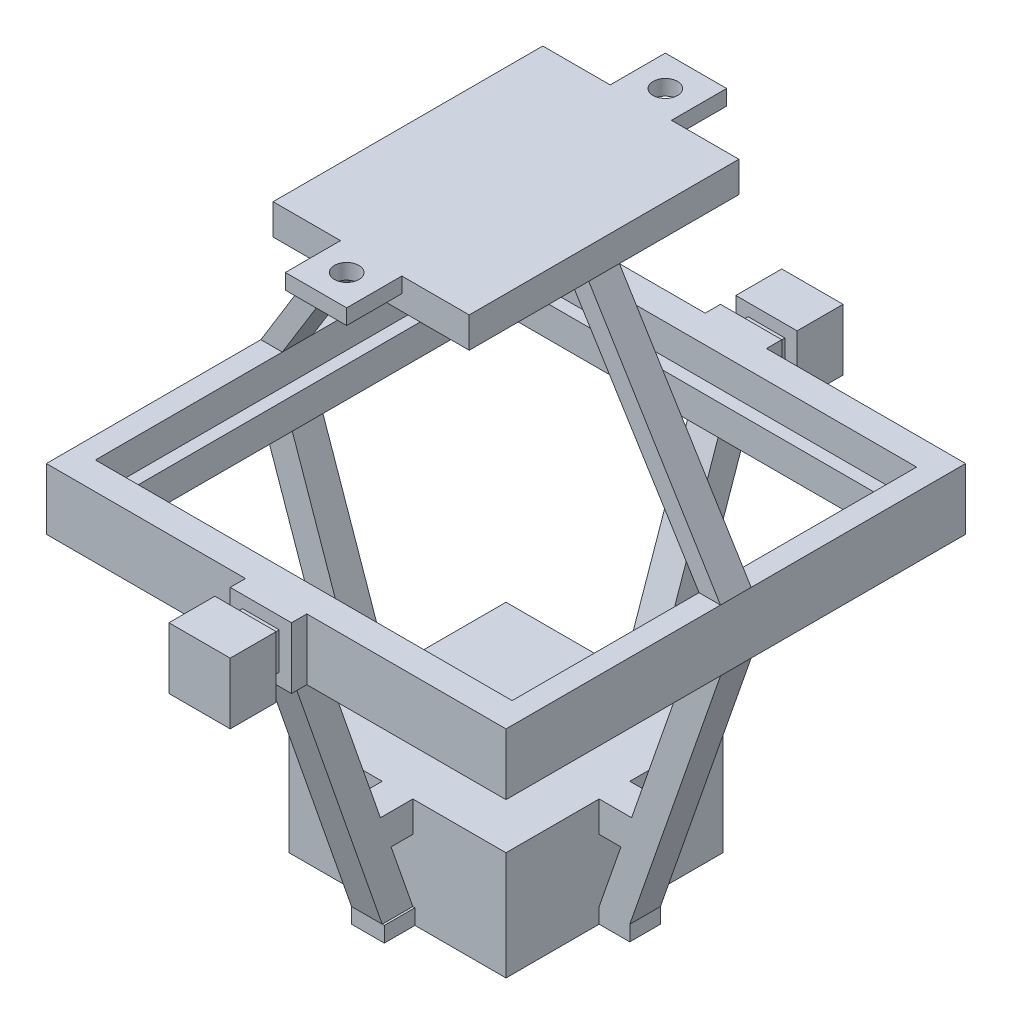
SolidWorks part; units mm, degrees
material "ABS PC"
ref_plane "Front Plane" through (0, 0, 0) normal (0, 0, 1) x (1, 0, 0)
ref_plane "Top Plane" through (0, 0, 0) normal (0, 1, 0) x (1, 0, 0)
ref_plane "Right Plane" through (0, 0, 0) normal (1, 0, 0) x (0, 0, -1)
sketch "Sketch2" plane through (0, 0, 0) normal (0, 1, 0) x (1, 0, 0)
  line L1 (-37.5, 37.5) -> (37.5, 37.5)
  line L2 (-37.5, 37.5) -> (-37.5, -37.5)
  line L3 (-37.5, -37.5) -> (37.5, -37.5)
  line L4 (37.5, 37.5) -> (37.5, -37.5)
  line L5 (-37.5, 37.5) -> (37.5, -37.5) construction
  line L6 (-37.5, -37.5) -> (37.5, 37.5) construction
  point P0 (0, 0)
extrude "Boss-Extrude1" add sketch "Sketch2" along normal blind 5
extrude "Boss-Extrude2" add sketch "Sketch2<2>" against normal blind 5
sketch "Sketch2<2>" plane through (0, 0, 0) normal (0, 1, 0) x (1, 0, 0) same geometry as "Sketch2"
sketch "Sketch4" plane through (0, 5, 0) normal (0, 1, 0) x (1, 0, 0)
  line L1 (-34, 33) -> (34, 33)
  line L2 (-34, 33) -> (-34, -33)
  line L3 (-34, -33) -> (34, -33)
  line L4 (34, 33) -> (34, -33)
  line L5 (-34, 33) -> (34, -33) construction
  line L6 (-34, -33) -> (34, 33) construction
  point P0 (0, 0)
extrude "Cut-Extrude1" cut sketch "Sketch4" against normal blind 5
sketch "Sketch5" plane through (0, 0, 0) normal (0, 1, 0) x (1, 0, 0)
  line L1 (-32, 31) -> (32, 31)
  line L2 (-32, 31) -> (-32, -31)
  line L3 (-32, -31) -> (32, -31)
  line L4 (32, 31) -> (32, -31)
  line L5 (-32, 31) -> (32, -31) construction
  line L6 (-32, -31) -> (32, 31) construction
  point P0 (0, 0)
extrude "Cut-Extrude2" cut sketch "Sketch5" against normal blind 5
sketch "Sketch6" plane through (0, 0, 37.5) normal (0, 0, 1) x (1, 0, 0)
  line L0 (-37.5, -5) -> (37.5, -5) construction
  line L1 (-5, 5) -> (5, 5)
  line L2 (-5, 5) -> (-5, -5)
  line L3 (-5, -5) -> (5, -5)
  line L4 (5, 5) -> (5, -5)
  line L5 (-5, 5) -> (5, -5) construction
  line L6 (-5, -5) -> (5, 5) construction
  point P0 (0, 0)
extrude "Boss-Extrude3" add sketch "Sketch6" along normal blind 2.5
sketch "Sketch7" plane through (0, 0, 40) normal (0, 0, 1) x (1, 0, 0)
  line L1 (-3, 3) -> (3, 3)
  line L2 (-3, 3) -> (-3, -3)
  line L3 (-3, -3) -> (3, -3)
  line L4 (3, 3) -> (3, -3)
  line L5 (-3, 3) -> (3, -3) construction
  line L6 (-3, -3) -> (3, 3) construction
  point P0 (0, 0)
extrude "Boss-Extrude4" add sketch "Sketch7" along normal blind 2.5
sketch "Sketch8" plane through (0, 0, 42.5) normal (0, 0, 1) x (1, 0, 0)
  line L1 (-5, 5) -> (5, 5)
  line L2 (-5, 5) -> (-5, -5)
  line L3 (-5, -5) -> (5, -5)
  line L4 (5, 5) -> (5, -5)
  line L5 (-5, 5) -> (5, -5) construction
  line L6 (-5, -5) -> (5, 5) construction
  point P0 (0, 0)
extrude "Boss-Extrude5" add sketch "Sketch8" along normal blind 7.5
sketch "Sketch9" plane through (0, 0, -37.5) normal (0, 0, -1) x (-1, 0, 0)
  line L1 (-5, 5) -> (5, 5)
  line L2 (-5, 5) -> (-5, -5)
  line L3 (-5, -5) -> (5, -5)
  line L4 (5, 5) -> (5, -5)
  line L5 (-5, 5) -> (5, -5) construction
  line L6 (-5, -5) -> (5, 5) construction
  point P0 (0, 0)
extrude "Boss-Extrude6" add sketch "Sketch9" along normal blind 2.5
sketch "Sketch10" plane through (0, 0, -40) normal (0, 0, -1) x (-1, 0, 0)
  line L1 (-3, 3) -> (3, 3)
  line L2 (-3, 3) -> (-3, -3)
  line L3 (-3, -3) -> (3, -3)
  line L4 (3, 3) -> (3, -3)
  line L5 (-3, 3) -> (3, -3) construction
  line L6 (-3, -3) -> (3, 3) construction
  point P0 (0, 0)
extrude "Boss-Extrude7" add sketch "Sketch10" along normal blind 2.5
sketch "Sketch11" plane through (0, 0, -42.5) normal (0, 0, -1) x (-1, 0, 0)
  line L1 (-5, 5) -> (5, 5)
  line L2 (-5, 5) -> (-5, -5)
  line L3 (-5, -5) -> (5, -5)
  line L4 (5, 5) -> (5, -5)
  line L5 (-5, 5) -> (5, -5) construction
  line L6 (-5, -5) -> (5, 5) construction
  point P0 (0, 0)
extrude "Boss-Extrude8" add sketch "Sketch11" along normal blind 7.5
ref_plane "Plane1" through (0, 50, 0) normal (0, 1, 0) x (1, 0, 0)
ref_plane "Plane3" through (0, 45, 0) normal (0, 1, 0) x (1, 0, 0)
ref_plane "Plane4" through (0, -50, 0) normal (0, 1, 0) x (1, 0, 0)
sketch "Sketch14" plane through (0, -50, 0) normal (0, 1, 0) x (1, 0, 0)
  line L1 (17.7, 17.7) -> (-17.7, 17.7)
  line L2 (17.7, 17.7) -> (17.7, -17.7)
  line L3 (17.7, -17.7) -> (-17.7, -17.7)
  line L4 (-17.7, 17.7) -> (-17.7, -17.7)
  line L5 (17.7, 17.7) -> (-17.7, -17.7) construction
  line L6 (17.7, -17.7) -> (-17.7, 17.7) construction
  point P0 (0, 0)
extrude "Boss-Extrude9" add sketch "Sketch14" along normal blind 17.7 separate body
sketch "Sketch15" plane through (0, -50, 0) normal (0, -1, 0) x (1, 0, 0)
  line L1 (-12.7, 12.7) -> (12.7, 12.7)
  line L2 (-12.7, 12.7) -> (-12.7, -12.7)
  line L3 (-12.7, -12.7) -> (12.7, -12.7)
  line L4 (12.7, 12.7) -> (12.7, -12.7)
  line L5 (-12.7, 12.7) -> (12.7, -12.7) construction
  line L6 (-12.7, -12.7) -> (12.7, 12.7) construction
  point P0 (0, 0)
extrude "Cut-Extrude3" cut sketch "Sketch15" against normal blind 12.7
extrude "Cut-Extrude6" cut sketch "Sketch32" against normal blind 5
sketch "Sketch32" plane through (0, -32.3, 0) normal (0, 1, 0) x (1, 0, 0)
  circle A0 centre (0, 0) radius 3
sketch "Sketch16" plane through (0, 45, 0) normal (0, 1, 0) x (1, 0, 0)
  line L1 (-16, 22) -> (16, 22)
  line L2 (-16, 22) -> (-16, -22)
  line L3 (-16, -22) -> (16, -22)
  line L4 (16, 22) -> (16, -22)
  line L5 (-16, 22) -> (16, -22) construction
  line L6 (-16, -22) -> (16, 22) construction
  point P0 (0, 0)
extrude "Boss-Extrude10" add sketch "Sketch16" against normal blind 5 separate body
sketch "Sketch18" plane through (0, 45, 0) normal (0, 1, 0) x (1, 0, 0)
  line L21 (16, 22) -> (-16, 22) construction
  line L22 (-5, 22) -> (5, 22)
  line L23 (-5, 22) -> (-5, 31)
  line L24 (-5, 31) -> (5, 31)
  line L25 (5, 22) -> (5, 31)
  line L26 (32, 31) -> (-32, 31) construction
  line L33 (-16, -22) -> (16, -22) construction
  line L34 (-5, -22) -> (5, -22)
  line L35 (-5, -22) -> (-5, -31)
  line L36 (-5, -31) -> (5, -31)
  line L37 (5, -22) -> (5, -31)
  line L38 (-32, -31) -> (32, -31) construction
extrude "Boss-Extrude12" add sketch "Sketch18" against normal blind 2.5
sketch "Sketch21" plane through (0, 0, 0) normal (0, 0, 1) x (1, 0, 0)
  line L0 (-37.5, 5) -> (-34, 5)
  line L1 (-37.5, 5) -> (-5, 5) construction
  line L2 (-37.5, 5) -> (-16, 40)
  line L3 (-34, 5) -> (-12.4348, 40)
  line L4 (-16, 40) -> (16, 40) construction
  line L5 (-12.4348, 40) -> (-16, 40)
  line L6 (37.5, 5) -> (34, 5)
  line L7 (5, 5) -> (37.5, 5) construction
  line L8 (37.5, 5) -> (16, 40)
  line L9 (34, 5) -> (12.2456, 40)
  line L10 (12.2456, 40) -> (16, 40)
extrude "Boss-Extrude13" add sketch "Sketch21" along normal blind 2.5
extrude "Boss-Extrude14" add sketch "Sketch21<2>" against normal blind 2.5
sketch "Sketch21<2>" plane through (0, 0, 0) normal (0, 0, 1) x (1, 0, 0) same geometry as "Sketch21"
sketch "Sketch31" plane through (0, 45, 0) normal (0, 1, 0) x (1, 0, 0)
  line L0 (0, -30.25) -> (0, 30.25) construction
  circle A0 centre (0, 26) radius 2
  circle A1 centre (0, -26) radius 2
extrude "Charger Support Holes" cut sketch "Sketch31" against normal blind 2.5
sketch "Sketch27" plane through (0, -50, 0) normal (0, -1, 0) x (-1, 0, 0)
  line L0 (-17.7, -17.7) -> (-17.7, 17.7) construction
  line L1 (-12.2456, -2.5) -> (-34, -2.5) construction
  line L2 (-17.7, -2.5) -> (-22.7, -2.5)
  line L3 (-17.7, -2.5) -> (-17.7, 2.5)
  line L4 (-17.7, 2.5) -> (-22.7, 2.5)
  line L5 (-22.7, -2.5) -> (-22.7, 2.5)
  line L6 (-12.2456, 2.5) -> (-34, 2.5) construction
  line L21 (17.7, 17.7) -> (17.7, -17.7) construction
  line L22 (34, -2.5) -> (12.4348, -2.5) construction
  line L23 (34, 2.5) -> (12.4348, 2.5) construction
  line L26 (17.7, -2.5) -> (22.7, -2.5)
  line L27 (17.7, -2.5) -> (17.7, 2.5)
  line L28 (17.7, 2.5) -> (22.7, 2.5)
  line L29 (22.7, -2.5) -> (22.7, 2.5)
  line L33 (17.7, -17.7) -> (-17.7, -17.7) construction
  line L34 (2.5, -17.7) -> (-2.8444, -17.7)
  line L35 (2.5, -17.7) -> (2.5, -22.7)
  line L36 (2.5, -22.7) -> (-2.8444, -22.7)
  line L37 (-2.8444, -17.7) -> (-2.8444, -22.7)
  line L39 (-17.7, 17.7) -> (17.7, 17.7) construction
  line L44 (2.5, 17.7) -> (-2.5, 17.7)
  line L45 (2.5, 17.7) -> (2.5, 22.7)
  line L46 (2.5, 22.7) -> (-2.5, 22.7)
  line L47 (-2.5, 17.7) -> (-2.5, 22.7)
extrude "Eyebolt Bolt Supports" add sketch "Sketch27" against normal blind 2.5
sketch "Sketch28" plane through (0, 0, 0) normal (0, 0, 1) x (1, 0, 0)
  line L0 (22.7, -47.5) -> (37.5, -5)
  line L1 (37.5, -5) -> (32.5, -5)
  line L2 (5, -5) -> (37.5, -5) construction
  line L3 (32.5, -5) -> (17.7, -47.5)
  line L4 (17.7, -47.5) -> (22.7, -47.5)
  line L5 (-22.7, -47.5) -> (-37.5, -5)
  line L6 (-37.5, -5) -> (-32.5, -5)
  line L7 (-32.5, -5) -> (-17.7, -47.5)
  line L8 (-17.7, -47.5) -> (-22.7, -47.5)
extrude "Boss-Extrude15" add sketch "Sketch28" along normal blind 2.5
extrude "Boss-Extrude16" add sketch "Sketch28<2>" against normal blind 2.5
sketch "Sketch28<2>" plane through (0, 0, 0) normal (0, 0, 1) x (1, 0, 0) same geometry as "Sketch28"
sketch "Sketch30" plane through (0, 0, 0) normal (1, 0, 0) x (0, 0, -1)
  line L0 (22.7, -47.5) -> (37.5, -5)
  line L1 (37.5, -5) -> (32.5, -5)
  line L2 (2.5, -5) -> (37.5, -5) construction
  line L3 (22.7, -47.5) -> (17.7, -47.5)
  line L4 (17.7, -47.5) -> (32.5, -5)
  line L5 (-37.5, -5) -> (-22.7, -47.5)
  line L7 (-22.7, -47.5) -> (-17.7, -47.5)
  line L8 (-17.7, -47.5) -> (-32.5, -5)
  line L9 (-37.5, -5) -> (-2.5, -5) construction
  line L10 (-32.5, -5) -> (-37.5, -5)
extrude "Boss-Extrude17" add sketch "Sketch30" along normal blind 2.5
extrude "Boss-Extrude18" add sketch "Sketch30<2>" against normal blind 2.5
sketch "Sketch30<2>" plane through (0, 0, 0) normal (1, 0, 0) x (0, 0, -1) same geometry as "Sketch30"
sketch "Sketch33" plane through (0, -32.3, 0) normal (0, 1, 0) x (1, 0, 0)
  line L0 (17.7, -17.7) -> (17.7, 17.7) construction
  line L1 (17.7, 2.5) -> (24, 2.5)
  line L2 (17.7, 2.5) -> (17.7, -2.5)
  line L3 (17.7, -2.5) -> (24, -2.5)
  line L4 (24, 2.5) -> (24, -2.5)
  line L5 (17.7, 17.7) -> (-17.7, 17.7) construction
  line L6 (2.5, 17.7) -> (-2.5, 17.7)
  line L7 (2.5, 17.7) -> (2.5, 24)
  line L8 (2.5, 24) -> (-2.5, 24)
  line L9 (-2.5, 17.7) -> (-2.5, 24)
  line L10 (-17.7, 17.7) -> (-17.7, -17.7) construction
  line L11 (-17.7, 2.5) -> (-24, 2.5)
  line L12 (-17.7, 2.5) -> (-17.7, -2.5)
  line L13 (-17.7, -2.5) -> (-24, -2.5)
  line L14 (-24, 2.5) -> (-24, -2.5)
  line L16 (-2.5, -17.7) -> (2.5, -17.7)
  line L17 (-2.5, -17.7) -> (-2.5, -24)
  line L18 (-2.5, -24) -> (2.5, -24)
  line L19 (2.5, -17.7) -> (2.5, -24)
extrude "Eyebolt Mini Supports " add sketch "Sketch33" against normal blind 5
